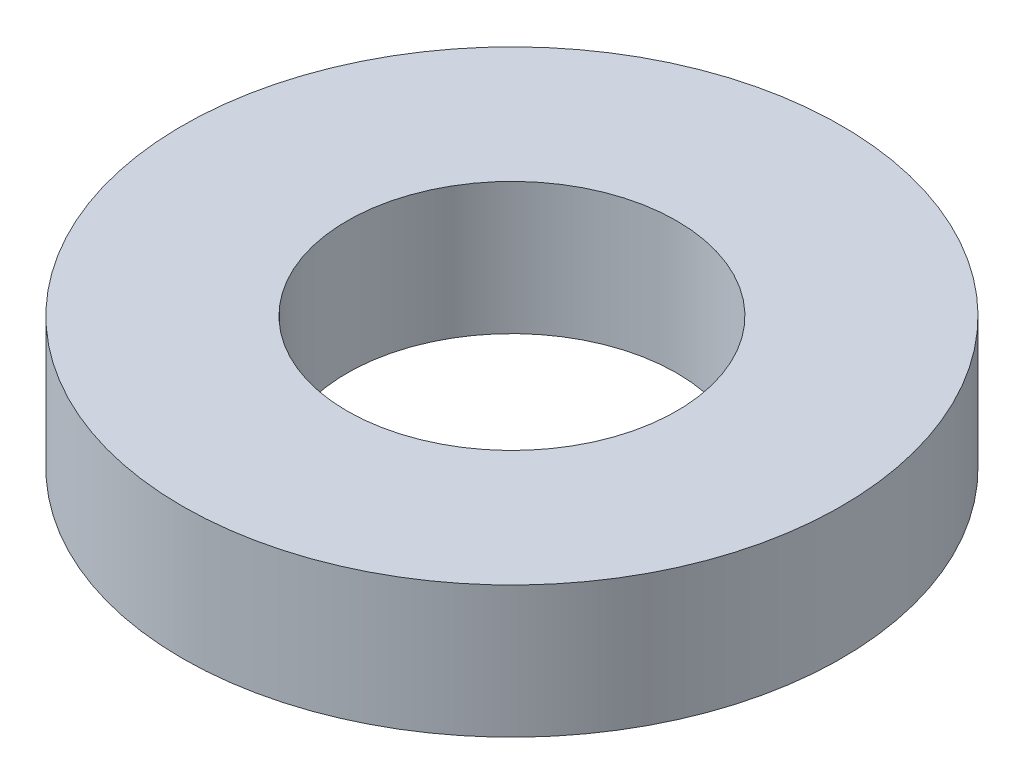
SolidWorks part; units mm, degrees
ref_plane "Front Plane" through (0, 0, 0) normal (0, 0, 1) x (1, 0, 0)
ref_plane "Top Plane" through (0, 0, 0) normal (0, 1, 0) x (1, 0, 0)
ref_plane "Right Plane" through (0, 0, 0) normal (1, 0, 0) x (0, 0, -1)
sketch "Sketch1" plane through (0, 0, 0) normal (0, 1, 0) x (1, 0, 0)
  circle A0 centre (0, 0) radius 60
  dimension "FLANGE_OD" = 120
extrude "Boss-Extrude1" add sketch "Sketch1" along normal blind 24
sketch "Sketch2" plane through (0, 0, 0) normal (0, 1, 0) x (1, 0, 0)
  circle A0 centre (0, 0) radius 30
  dimension "BORE_D" = 60
extrude "Cut-Extrude1" cut sketch "Sketch2" along normal through all
sketch "Sketch3" plane through (0, 24, 0) normal (0, 1, 0) x (1, 0, 0)
  circle A0 centre (0, 0) radius 21.8419 construction
  circle A1 centre (-21.8419, 0) radius 2.6611
  dimension "BOLT_D" = 5.3222
  dimension "BOLT_PCD" = 43.6838
extrude "Cut-Extrude2" cut sketch "Sketch3" against normal blind 17.8047 rebuild error yes
pattern_circular "CirPattern1" count 4 over 360 rebuild error yes
